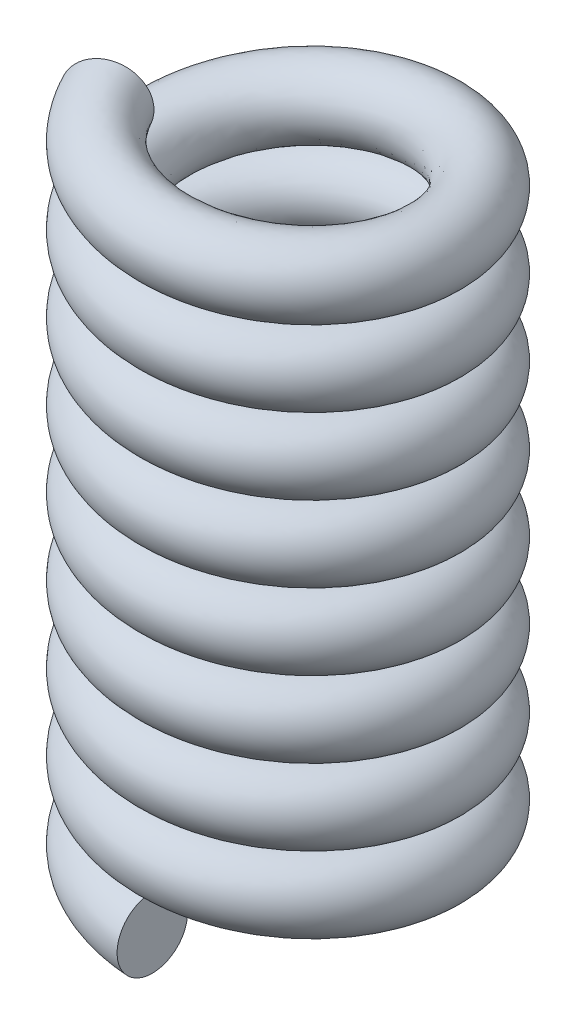
SolidWorks part; units mm, degrees
material "1.8159 (51CrV4)"
ref_plane "E_Oben" through (0, 0, 0) normal (0, 0, 1) x (1, 0, 0)
ref_plane "E_Vorne" through (0, 0, 0) normal (0, 1, 0) x (1, 0, 0)
ref_plane "E_Rechts" through (0, 0, 0) normal (1, 0, 0) x (0, 0, -1)
sketch "Skizze4" plane through (0, 0, 0) normal (0, 1, 0) x (1, 0, 0)
  circle A0 centre (0, 0) radius 50
  dimension "D1" = 100
curve "Spirale/Helix1" pitch 28 height 229 radius 50 left hand yes centre (0, 0, 0) axis (0, 1, 0) start towards (0, 0, 1)
sketch "Skizze5" plane through (0, 0, 0) normal (1, 0, 0) x (0, 0, -1)
  line L2 (55, 0) -> (-55, 0) construction
  circle A1 centre (-50, 0) radius 13
  spline S0 degree 3 poles (-50, 0) (-50, 0.2965) (-49.3314, 0.8913) (-46.3629, 1.782) (-41.5468, 2.6732) (-35.0753, 3.5642) (-27.206, 4.4553) (-18.2527, 5.3463) (-8.5721, 6.2374) (1.4501, 7.1284) (11.4146, 8.0195) (20.9242, 8.9105) (29.6, 9.8016) (37.0963, 10.6926) (43.1144, 11.5837) (47.4146, 12.4747) (49.8254, 13.3658) (50.2507, 14.2568) (48.6737, 15.1479) (45.1572, 16.0389) (39.8413, 16.93) (32.9378, 17.821) (24.7218, 18.7121) (15.5207, 19.6031) (5.7012, 20.4942) (-4.3456, 21.3852) (-14.2191, 22.2763) (-23.5261, 23.1673) (-31.8956, 24.0584) (-38.9942, 24.9494) (-44.5389, 25.8405) (-48.3089, 26.7315) (-50.1539, 27.6226) (-50.0003, 28.5136) (-47.8544, 29.4047) (-43.8016, 30.2957) (-38.0035, 31.1868) (-30.6909, 32.0778) (-22.1555, 32.9689) (-12.7372, 33.8599) (-2.8113, 34.751) (7.2266, 35.642) (16.9765, 36.5331) (26.05, 37.4241) (34.0854, 38.3152) (40.7626, 39.2062) (45.8155, 40.0973) (49.0428, 40.9883) (50.3158, 41.8794) (49.5839, 42.7704) (46.8762, 43.6615) (42.3006, 44.5525) (36.0395, 45.4436) (28.3422, 46.3346) (19.5156, 47.2257) (9.9113, 48.1167) (-0.0879, 49.0078) (-10.0836, 49.8988) (-19.6775, 50.7899) (-28.4873, 51.6809) (-36.162, 52.572) (-42.3957, 53.463) (-46.94, 54.3541) (-49.6139, 55.2451) (-50.3108, 56.1362) (-49.0029, 57.0272) (-45.7424, 57.9183) (-40.6592, 58.8093) (-33.9558, 59.7004) (-25.8994, 60.5914) (-16.8109, 61.4825) (-7.0526, 62.3735) (2.9868, 63.2646) (12.9072, 64.1556) (22.3132, 65.0467) (30.8301, 65.9377) (38.1185, 66.8288) (43.888, 67.7198) (47.9086, 68.6109) (50.0202, 69.5019) (50.1387, 70.393) (48.2592, 71.284) (44.4567, 72.1751) (38.8828, 73.0661) (31.7594, 73.9572) (23.3706, 74.8482) (14.0504, 75.7393) (4.1704, 76.6304) (-5.8758, 77.5214) (-15.6878, 78.4125) (-24.8748, 79.3035) (-33.0705, 80.1946) (-39.9485, 81.0856) (-45.2346, 81.9767) (-48.7182, 82.8677) (-50.2605, 83.7588) (-49.8001, 84.6498) (-47.3553, 85.5409) (-43.0235, 86.4319) (-36.9773, 87.323) (-29.4576, 88.214) (-20.7641, 89.1051) (-11.2433, 89.9961) (-1.2744, 90.8872) (8.7453, 91.7782) (18.4164, 92.6693) (27.3538, 93.5603) (35.2011, 94.4514) (41.6458, 95.3424) (46.431, 96.2335) (49.3661, 97.1245) (50.334, 98.0156) (49.2962, 98.9066) (46.2941, 99.7977) (41.4473, 100.6887) (34.949, 101.5798) (27.058, 102.4708) (18.0888, 103.3619) (8.3988, 104.2529) (-1.6258, 105.144) (-11.5857, 106.035) (-21.0839, 106.9261) (-29.742, 107.8171) (-37.2149, 108.7082) (-43.2049, 109.5992) (-47.4733, 110.4903) (-49.85, 111.3813) (-50.2403, 112.2724) (-48.6286, 113.1634) (-45.0793, 114.0545) (-39.7336, 114.9455) (-32.8046, 115.8366) (-24.5685, 116.7276) (-15.3534, 117.6187) (-5.5265, 118.5097) (4.5207, 119.4008) (14.3877, 120.2918) (23.6814, 121.1829) (32.0314, 122.0739) (39.1051, 122.965) (44.6205, 123.856) (48.3579, 124.7471) (50.1684, 125.6381) (49.9798, 126.5292) (47.7996, 127.4202) (43.7148, 128.3113) (37.888, 129.2023) (30.5514, 130.0934) (21.9975, 130.9844) (12.567, 131.8755) (2.6358, 132.7665) (-7.4005, 133.6576) (-17.1419, 134.5486) (-26.2002, 135.4397) (-34.2145, 136.3307) (-40.8655, 137.2218) (-45.888, 138.1128) (-49.0821, 139.0039) (-50.3203, 139.8949) (-49.5534, 140.786) (-46.8119, 141.677) (-42.2051, 142.5681) (-35.9165, 143.4591) (-28.1968, 144.3502) (-19.3534, 145.2412) (-9.7389, 146.1323) (0.2637, 147.0233) (10.2558, 147.9144) (19.8392, 148.8054) (28.6321, 149.6965) (36.284, 150.5875) (42.4902, 151.4786) (47.0032, 152.3696) (49.6432, 153.2607) (50.3051, 154.1518) (48.9625, 155.0428) (45.6688, 155.9339) (40.5553, 156.8249) (33.8258, 157.716) (25.7485, 158.607) (16.6451, 159.4981) (6.8785, 160.3891) (-3.1623, 161.2802) (-13.077, 162.1712) (-22.4706, 163.0623) (-30.9689, 163.9533) (-38.2331, 164.8444) (-43.9738, 165.7354) (-47.9623, 166.6265) (-50.0395, 167.5175) (-50.1229, 168.4086) (-48.209, 169.2996) (-44.374, 170.1907) (-38.7709, 171.0817) (-31.6229, 171.9728) (-23.2147, 172.8638) (-13.8815, 173.7549) (-3.9952, 174.6459) (6.0503, 175.537) (15.8548, 176.428) (25.0275, 177.3191) (33.2028, 178.2101) (40.0552, 179.1012) (45.3114, 179.9922) (48.7621, 180.8833) (50.2698, 181.7743) (49.7743, 182.6654) (47.2954, 183.5564) (42.932, 184.4475) (36.8578, 185.3385) (29.3149, 186.2296) (20.6039, 187.1206) (11.0719, 188.0117) (1.0986, 188.9027) (-8.9183, 189.7938) (-18.5799, 190.6848) (-27.5012, 191.5759) (-35.3266, 192.4669) (-41.7443, 193.358) (-46.4986, 194.249) (-49.4001, 195.1401) (-50.3331, 196.0311) (-49.2604, 196.9222) (-46.2248, 197.8132) (-41.3473, 198.7043) (-34.8222, 199.5953) (-26.9096, 200.4864) (-17.9246, 201.3774) (-8.2254, 202.2685) (1.8015, 203.1595) (11.7567, 204.0506) (21.2434, 204.9416) (29.8836, 205.8327) (37.333, 206.7237) (43.2948, 207.6148) (47.5314, 208.5058) (49.874, 209.3969) (50.2292, 210.2879) (48.583, 211.179) (45.0008, 212.07) (39.6254, 212.9611) (32.6711, 213.8521) (24.4149, 214.7432) (15.1859, 215.6342) (5.3517, 216.5253) (-4.6957, 217.4163) (-14.5561, 218.3074) (-23.8364, 219.1984) (-32.1668, 220.0895) (-39.2155, 220.9805) (-44.7016, 221.8716) (-48.4064, 222.7626) (-50.1824, 223.6537) (-49.9587, 224.5447) (-47.7442, 225.4358) (-43.6275, 226.3268) (-37.7714, 227.218) (-30.4138, 228.1087) (-24.6917, 228.7035) (-21.6942, 229) knots 0 0 0 0 0.003891 0.007782 0.011673 0.015564 0.019455 0.023346 0.027237 0.031128 0.035019 0.038911 0.042802 0.046693 0.050584 0.054475 0.058366 0.062257 0.066148 0.070039 0.07393 0.077821 0.081712 0.085603 0.089494 0.093385 0.097276 0.101167 0.105058 0.108949 0.11284 0.116732 0.120623 0.124514 0.128405 0.132296 0.136187 0.140078 0.143969 0.14786 0.151751 0.155642 0.159533 0.163424 0.167315 0.171206 0.175097 0.178988 0.182879 0.18677 0.190661 0.194553 0.198444 0.202335 0.206226 0.210117 0.214008 0.217899 0.22179 0.225681 0.229572 0.233463 0.237354 0.241245 0.245136 0.249027 0.252918 0.256809 0.2607 0.264591 0.268482 0.272374 0.276265 0.280156 0.284047 0.287938 0.291829 0.29572 0.299611 0.303502 0.307393 0.311284 0.315175 0.319066 0.322957 0.326848 0.330739 0.33463 0.338521 0.342412 0.346304 0.350195 0.354086 0.357977 0.361868 0.365759 0.36965 0.373541 0.377432 0.381323 0.385214 0.389105 0.392996 0.396887 0.400778 0.404669 0.40856 0.412451 0.416342 0.420233 0.424125 0.428016 0.431907 0.435798 0.439689 0.44358 0.447471 0.451362 0.455253 0.459144 0.463035 0.466926 0.470817 0.474708 0.478599 0.48249 0.486381 0.490272 0.494163 0.498054 0.501946 0.505837 0.509728 0.513619 0.51751 0.521401 0.525292 0.529183 0.533074 0.536965 0.540856 0.544747 0.548638 0.552529 0.55642 0.560311 0.564202 0.568093 0.571984 0.575875 0.579767 0.583658 0.587549 0.59144 0.595331 0.599222 0.603113 0.607004 0.610895 0.614786 0.618677 0.622568 0.626459 0.63035 0.634241 0.638132 0.642023 0.645914 0.649805 0.653696 0.657588 0.661479 0.66537 0.669261 0.673152 0.677043 0.680934 0.684825 0.688716 0.692607 0.696498 0.700389 0.70428 0.708171 0.712062 0.715953 0.719844 0.723735 0.727626 0.731518 0.735409 0.7393 0.743191 0.747082 0.750973 0.754864 0.758755 0.762646 0.766537 0.770428 0.774319 0.77821 0.782101 0.785992 0.789883 0.793774 0.797665 0.801556 0.805447 0.809339 0.81323 0.817121 0.821012 0.824903 0.828794 0.832685 0.836576 0.840467 0.844358 0.848249 0.85214 0.856031 0.859922 0.863813 0.867704 0.871595 0.875486 0.879377 0.883268 0.88716 0.891051 0.894942 0.898833 0.902724 0.906615 0.910506 0.914397 0.918288 0.922179 0.92607 0.929961 0.933852 0.937743 0.941634 0.945525 0.949416 0.953307 0.957198 0.961089 0.964981 0.968872 0.972763 0.976654 0.980545 0.984436 0.988327 0.992218 0.996109 1 1 1 1 construction
  dimension "D1" = 26
sweep "Austragung2" add profiles "Skizze5" path "Spirale/Helix1"
